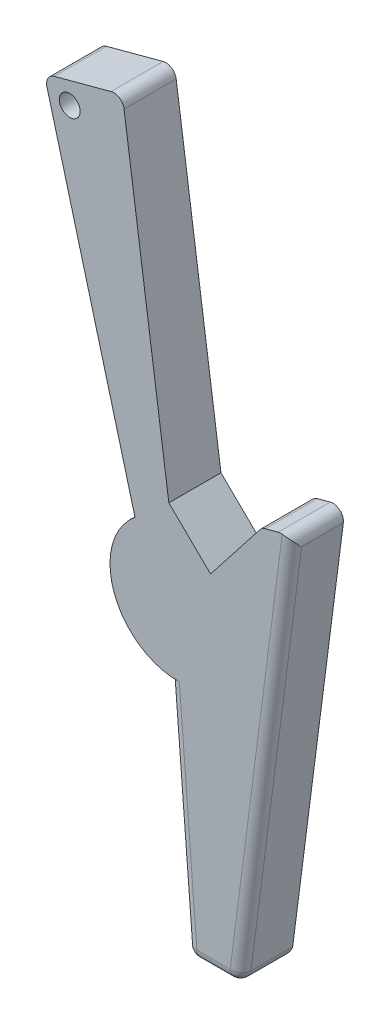
SolidWorks part; units mm, degrees
ref_plane "Front Plane" through (0, 0, 0) normal (0, 0, 1) x (1, 0, 0)
ref_plane "Top Plane" through (0, 0, 0) normal (0, 1, 0) x (1, 0, 0)
ref_plane "Right Plane" through (0, 0, 0) normal (1, 0, 0) x (0, 0, -1)
sketch "Sketch3" plane through (0, 0, 0) normal (0, 0, 1) x (1, 0, 0)
  line L0 (-163.8316, 25.0875) -> (3.0144, 25.0875) construction
  line L1 (-32.2609, 25.0875) -> (-47.2609, 21.0682)
  line L2 (-47.2609, 21.0682) -> (-29.8442, -43.9318)
  line L3 (-32.2609, 25.0875) -> (-23.3539, -38.2897)
  line L4 (-23.3539, -38.2897) -> (-15.3539, -46.1077)
  line L5 (-15.3539, -46.1077) -> (-5.494, -33.5068)
  line L6 (-5.494, -33.5068) -> (0.506, -31.8991)
  line L7 (0.506, -31.8991) -> (-9.8211, -111.8991)
  line L8 (-9.8211, -111.8991) -> (-19.8211, -111.8991)
  line L9 (-19.8211, -111.8991) -> (-23.3539, -66.8991)
  arc A0 (-23.3539, -66.8991) -> (-29.8442, -43.9318) centre (-21.6365, -54.013) cw
  dimension "D10" = 13
  dimension "D1" = 15
  dimension "D2" = 15
  dimension "D3" = 65
  dimension "D4" = 83
  dimension "D5" = 64
  dimension "D6" = 8
  dimension "D7" = 16
  dimension "D8" = 6
  dimension "D9" = 80
  dimension "D11" = 45
  dimension "D12" = 10
extrude "Boss-Extrude1" add sketch "Sketch3" along normal blind 10
sketch "Sketch5" plane through (0, 0, 10) normal (0, 0, 1) x (1, 0, 0)
  line L0 (-32.2609, 25.0875) -> (-47.2609, 21.0682) construction
  line L1 (-47.2609, 21.0682) -> (-29.8442, -43.9318) construction
  circle A0 centre (-42.362, 18.2398) radius 2
  dimension "D1" = 4
  dimension "D2" = 4
  dimension "D3" = 4
extrude "Cut-Extrude1" cut sketch "Sketch5" against normal through all
fillet "Fillet3" radius 2 10 edges at (-4.6575, -71.8991, 10) (-21.5875, -89.3991, 0) (-21.5875, -89.3991, 10) (-14.8211, -111.8991, 0) (-14.8211, -111.8991, 10) (-9.8211, -111.8991, 5) (0.506, -31.8991, 5) (-5.494, -33.5068, 5) (-32.2609, 25.0875, 5) (-47.2609, 21.0682, 5)
fillet "Fillet4" radius 2 3 edges at (-19.2795, -111.3133, 9.4142) (-19.2795, -111.3133, 0.5858) (-19.8211, -111.8991, 5)
